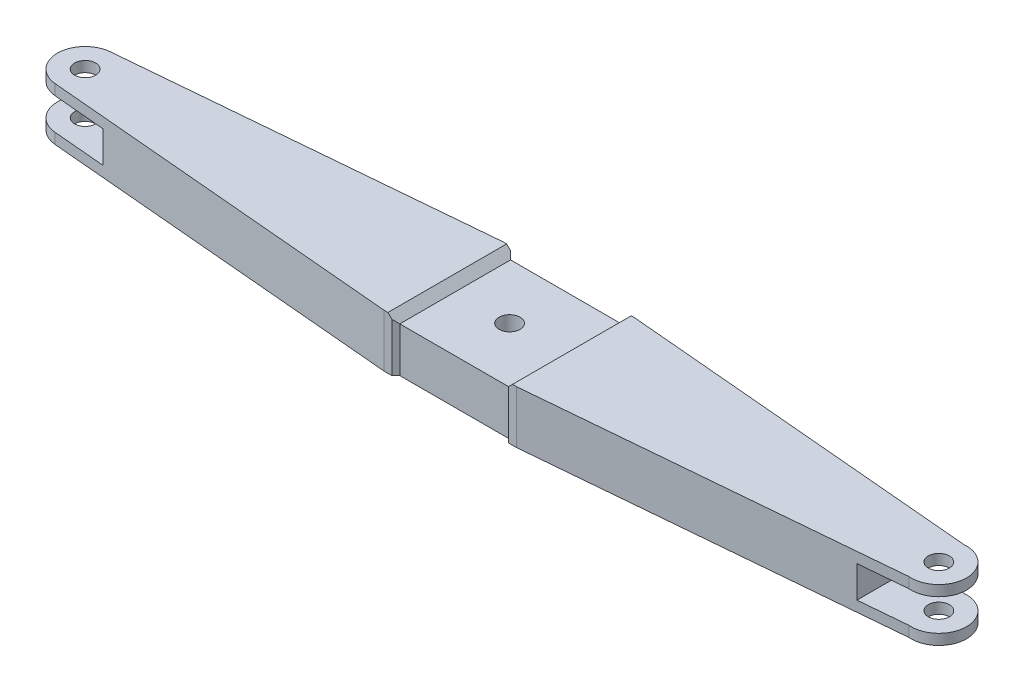
SolidWorks part; units mm, degrees
ref_plane "Alzado" through (0, 0, 0) normal (0, 0, 1) x (1, 0, 0)
ref_plane "Planta" through (0, 0, 0) normal (0, 1, 0) x (1, 0, 0)
ref_plane "Vista lateral" through (0, 0, 0) normal (1, 0, 0) x (0, 0, -1)
sketch "Croquis1" plane through (0, 0, 0) normal (0, 1, 0) x (1, 0, 0)
  line L0 (20.61, 21) -> (22.1098, 22.4998)
  line L1 (-20.61, -21) -> (20.61, -21)
  line L3 (-20.61, 21) -> (20.61, 21)
  line L5 (-20.61, -21) -> (20.61, 21) construction
  line L6 (-20.61, 21) -> (20.61, -21) construction
  line L7 (-20.61, 21) -> (-22.1098, 22.4998)
  line L8 (20.61, -21) -> (22.1098, -22.4998)
  line L9 (-20.61, -21) -> (-22.1098, -22.4998)
  line L10 (22.1098, 22.4998) -> (25.1098, 22.4998)
  line L11 (22.1098, -22.4998) -> (25.1098, -22.4998)
  line L12 (-22.1098, -22.4998) -> (-25.1098, -22.4998)
  line L13 (-22.1098, 22.4998) -> (-25.1098, 22.4998)
  line L14 (-25.1098, 22.4998) -> (-161.8206, 10.4598)
  line L15 (-25.1098, -22.4998) -> (-161.8206, -10.4598)
  line L16 (25.1098, 22.4998) -> (161.8206, 10.4598)
  line L17 (25.1098, -22.4998) -> (161.8206, -10.4598)
  arc A0 (161.8206, -10.4598) -> (161.8206, 10.4598) centre (162.7382, 0) ccw
  arc A1 (-161.8206, 10.4598) -> (-161.8206, -10.4598) centre (-160.903, 0) ccw
  circle A2 centre (-160.903, 0) radius 4
  circle A3 centre (162.7382, 0) radius 4
  point P0 (0, 0)
  dimension "D18" = 10.5
  dimension "D19" = 10.5
  dimension "D20" = 8
  dimension "D21" = 8
  dimension "D1" = 42
  dimension "D2" = 41.22
  dimension "D3" = 2.121
  dimension "D4" = 3
  dimension "D5" = 135.001
  dimension "D6" = 135.001
  dimension "D7" = 135.001
  dimension "D8" = 135.001
  dimension "D9" = 137.24
  dimension "D10" = 135
  dimension "D11" = 135
  dimension "D12" = 135
  dimension "D13" = 135
  dimension "D14" = 174.966
  dimension "D15" = 174.966
  dimension "D16" = 174.966
  dimension "D17" = 174.966
extrude "Saliente-Extruir1" add sketch "Croquis1" along normal blind 20
sketch "Croquis2" plane through (0, 0, 21) normal (0, 0, 1) x (1, 0, 0)
  line L0 (-171.403, 20) -> (-171.403, 0) construction
  line L1 (-171.403, 4) -> (-141.903, 4)
  line L2 (-171.403, 4) -> (-171.403, 16)
  line L3 (-171.403, 16) -> (-141.903, 16)
  line L4 (-141.903, 4) -> (-141.903, 16)
  line L5 (-171.403, 4) -> (-141.903, 16) construction
  line L6 (-171.403, 16) -> (-141.903, 4) construction
  line L7 (-161.8206, 20) -> (-25.1098, 20) construction
  line L8 (-171.403, 0) -> (-161.8206, 0) construction
  line L9 (143.7382, 4) -> (173.2382, 4)
  line L10 (143.7382, 4) -> (143.7382, 16)
  line L11 (143.7382, 16) -> (173.2382, 16)
  line L12 (173.2382, 4) -> (173.2382, 16)
  line L13 (143.7382, 4) -> (173.2382, 16) construction
  line L14 (143.7382, 16) -> (173.2382, 4) construction
  line L15 (173.2382, 20) -> (161.8206, 20) construction
  line L16 (161.8206, 0) -> (173.2382, 0) construction
  line L18 (173.2382, 0) -> (173.2382, 20) construction
  point P0 (-156.653, 10)
  point P11 (158.4882, 10)
  dimension "D1" = 4
  dimension "D2" = 4
  dimension "D3" = 29.5
  dimension "D4" = 4
  dimension "D5" = 4
  dimension "D6" = 29.5
extrude "Cortar-Extruir1" cut sketch "Croquis2" against normal through all
sketch "Croquis3" plane through (0, 20, 0) normal (0, 1, 0) x (1, 0, 0)
  line L1 (-20.61, -21) -> (20.61, -21)
  line L2 (-20.61, -21) -> (-20.61, 21)
  line L3 (-20.61, 21) -> (20.61, 21)
  line L4 (20.61, -21) -> (20.61, 21)
  line L5 (-20.61, -21) -> (20.61, 21) construction
  line L6 (-20.61, 21) -> (20.61, -21) construction
  point P0 (0, 0)
extrude "Cortar-Extruir2" cut sketch "Croquis3" against normal blind 3
chamfer "Chaflán1" distance 3 angle 45 2 edges at (20.61, 20, 0) (-20.61, 20, 0)
sketch "Croquis4" plane through (0, 17, 0) normal (0, 1, 0) x (1, 0, 0)
  circle A0 centre (0, 0) radius 4
  dimension "D1" = 8
extrude "Cortar-Extruir3" cut sketch "Croquis4" against normal through all
